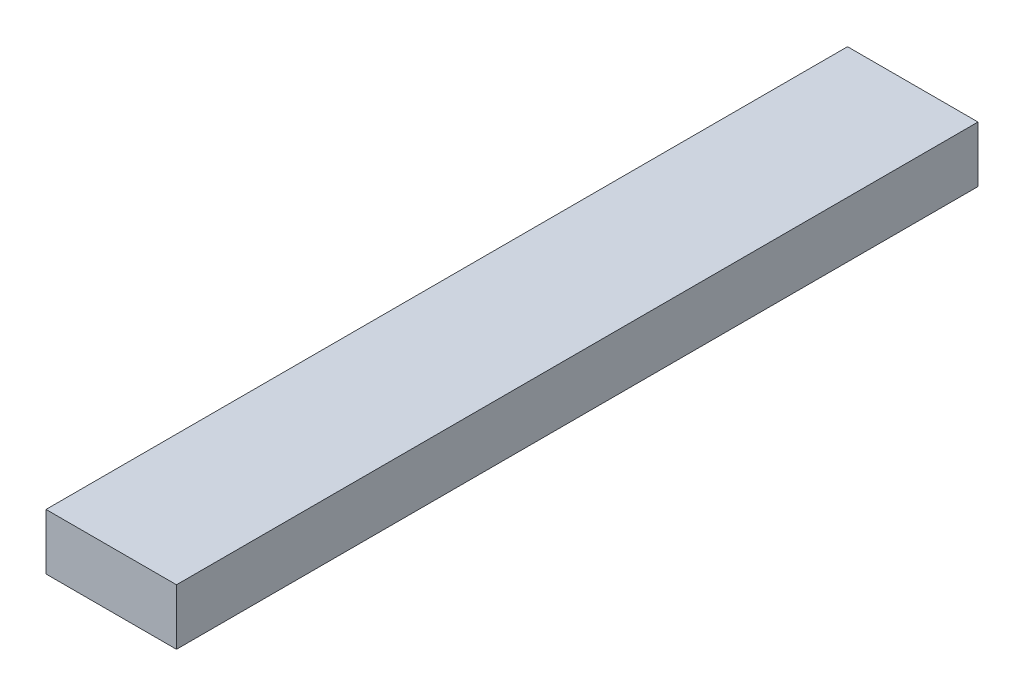
SolidWorks part; units mm, degrees
material "Pine"
ref_plane "Front Plane" through (0, 0, 0) normal (0, 0, 1) x (1, 0, 0)
ref_plane "Top Plane" through (0, 0, 0) normal (0, 1, 0) x (1, 0, 0)
ref_plane "Right Plane" through (0, 0, 0) normal (1, 0, 0) x (0, 0, -1)
sketch "Sketch1" plane through (0, 0, 0) normal (0, 0, 1) x (1, 0, 0)
  line L1 (0, 0) -> (88.9, 0)
  line L2 (0, 0) -> (0, 38.1)
  line L3 (0, 38.1) -> (88.9, 38.1)
  line L4 (88.9, 0) -> (88.9, 38.1)
  dimension "D1" = 88.9
  dimension "D2" = 38.1
extrude "Boss-Extrude1" add sketch "Sketch1" along normal blind 546.1
